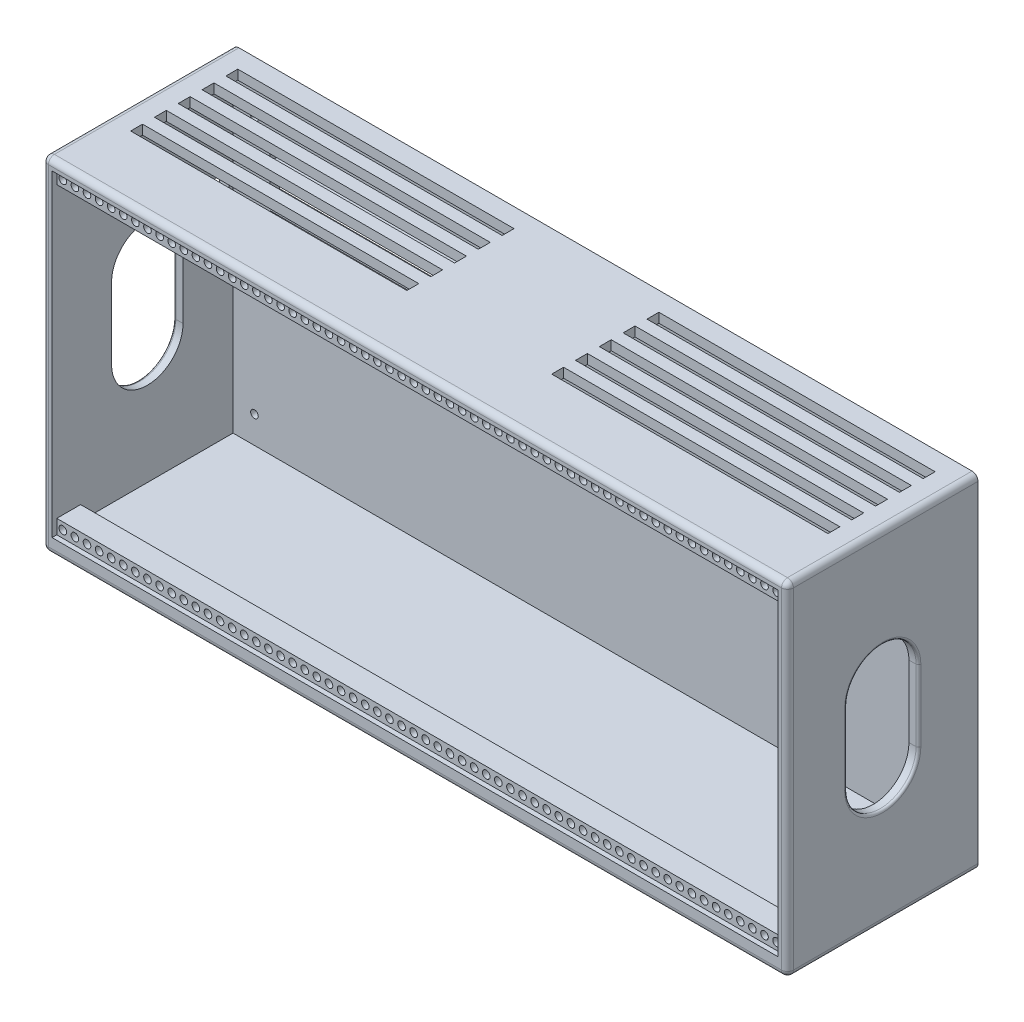
SolidWorks part; units mm, degrees
ref_plane "前视基准面" through (0, 0, 0) normal (0, 0, 1) x (1, 0, 0)
ref_plane "上视基准面" through (0, 0, 0) normal (0, 1, 0) x (1, 0, 0)
ref_plane "右视基准面" through (0, 0, 0) normal (1, 0, 0) x (0, 0, -1)
sketch "草图1" plane through (0, 0, 0) normal (0, 0, 1) x (1, 0, 0)
  line L0 (0, 0) -> (304.8, 0)
  line L2 (0, 133.35) -> (304.8, 133.35)
  line L3 (304.8, 133.35) -> (304.8, 0)
  line L4 (0, 133.35) -> (0, 137.35)
  line L5 (0, 137.35) -> (304.8, 137.35)
  line L6 (304.8, 137.35) -> (308.8, 137.35)
  line L7 (308.8, 137.35) -> (308.8, 0)
  line L8 (308.8, 0) -> (308.8, -6.6026)
  line L9 (308.8, -6.6026) -> (0, -6.6026)
  line L10 (0, -6.6026) -> (0, 0)
extrude "凸台-拉伸1" add sketch "草图1" along normal blind 80
ref_plane "基准面4" through (0, 0, 0) normal (0, 0, -1) x (-1, 0, 0)
sketch "草图2" plane through (0, 0, 0) normal (0, 0, -1) x (-1, 0, 0)
  line L0 (0, 133.35) -> (0, 0)
  line L1 (0, 0) -> (-304.8, 0)
  line L2 (-304.8, 0) -> (-304.8, 133.35)
  line L3 (-304.8, 133.35) -> (0, 133.35)
extrude "凸台-拉伸2" add sketch "草图2" against normal blind 4
ref_plane "基准面5" through (0, 0, 78) normal (0, 0, 1) x (1, 0, 0)
sketch "草图5" plane through (0, 0, 78) normal (0, 0, 1) x (1, 0, 0)
  line L0 (0, 133.35) -> (0, 127.35)
  line L1 (0, 0) -> (0, 133.35) construction
  line L2 (0, 127.35) -> (304.8, 127.35)
  line L3 (304.8, 133.35) -> (304.8, 0) construction
  line L4 (304.8, 127.35) -> (304.8, 133.35)
  line L5 (304.8, 133.35) -> (0, 133.35)
  line L6 (0, 0) -> (0, 6)
  line L7 (0, 6) -> (304.8, 6)
  line L8 (304.8, 133.35) -> (304.8, 0) construction
  line L9 (7.6, 3) -> (12.68, 3) construction
  line L10 (7.6, 130.35) -> (2.52, 130.35) construction
  line L11 (304.8, 6) -> (304.8, 0)
  line L12 (304.8, 0) -> (0, 0)
  circle A0 centre (7.6, 3) radius 1.6
  circle A1 centre (7.6, 130.35) radius 1.6
  circle A2 centre (12.68, 3) radius 1.6
  circle A3 centre (12.68, 130.35) radius 1.6
  circle A4 centre (17.76, 3) radius 1.6
  circle A5 centre (17.76, 130.35) radius 1.6
  circle A6 centre (22.84, 3) radius 1.6
  circle A7 centre (22.84, 130.35) radius 1.6
  circle A8 centre (27.92, 3) radius 1.6
  circle A9 centre (27.92, 130.35) radius 1.6
  circle A10 centre (33, 3) radius 1.6
  circle A11 centre (33, 130.35) radius 1.6
  circle A12 centre (38.08, 3) radius 1.6
  circle A13 centre (38.08, 130.35) radius 1.6
  circle A14 centre (43.16, 3) radius 1.6
  circle A15 centre (43.16, 130.35) radius 1.6
  circle A16 centre (48.24, 3) radius 1.6
  circle A17 centre (48.24, 130.35) radius 1.6
  circle A18 centre (53.32, 3) radius 1.6
  circle A19 centre (53.32, 130.35) radius 1.6
  circle A20 centre (58.4, 3) radius 1.6
  circle A21 centre (58.4, 130.35) radius 1.6
  circle A22 centre (63.48, 3) radius 1.6
  circle A23 centre (63.48, 130.35) radius 1.6
  circle A24 centre (68.56, 3) radius 1.6
  circle A25 centre (68.56, 130.35) radius 1.6
  circle A26 centre (73.64, 3) radius 1.6
  circle A27 centre (73.64, 130.35) radius 1.6
  circle A28 centre (78.72, 3) radius 1.6
  circle A29 centre (78.72, 130.35) radius 1.6
  circle A30 centre (83.8, 3) radius 1.6
  circle A31 centre (83.8, 130.35) radius 1.6
  circle A32 centre (88.88, 3) radius 1.6
  circle A33 centre (88.88, 130.35) radius 1.6
  circle A34 centre (93.96, 3) radius 1.6
  circle A35 centre (93.96, 130.35) radius 1.6
  circle A36 centre (99.04, 3) radius 1.6
  circle A37 centre (99.04, 130.35) radius 1.6
  circle A38 centre (104.12, 3) radius 1.6
  circle A39 centre (104.12, 130.35) radius 1.6
  circle A40 centre (109.2, 3) radius 1.6
  circle A41 centre (109.2, 130.35) radius 1.6
  circle A42 centre (114.28, 3) radius 1.6
  circle A43 centre (114.28, 130.35) radius 1.6
  circle A44 centre (119.36, 3) radius 1.6
  circle A45 centre (119.36, 130.35) radius 1.6
  circle A46 centre (124.44, 3) radius 1.6
  circle A47 centre (124.44, 130.35) radius 1.6
  circle A48 centre (129.52, 3) radius 1.6
  circle A49 centre (129.52, 130.35) radius 1.6
  circle A50 centre (134.6, 3) radius 1.6
  circle A51 centre (134.6, 130.35) radius 1.6
  circle A52 centre (139.68, 3) radius 1.6
  circle A53 centre (139.68, 130.35) radius 1.6
  circle A54 centre (144.76, 3) radius 1.6
  circle A55 centre (144.76, 130.35) radius 1.6
  circle A56 centre (149.84, 3) radius 1.6
  circle A57 centre (149.84, 130.35) radius 1.6
  circle A58 centre (154.92, 3) radius 1.6
  circle A59 centre (154.92, 130.35) radius 1.6
  circle A60 centre (160, 3) radius 1.6
  circle A61 centre (160, 130.35) radius 1.6
  circle A62 centre (165.08, 3) radius 1.6
  circle A63 centre (165.08, 130.35) radius 1.6
  circle A64 centre (170.16, 3) radius 1.6
  circle A65 centre (170.16, 130.35) radius 1.6
  circle A66 centre (175.24, 3) radius 1.6
  circle A67 centre (175.24, 130.35) radius 1.6
  circle A68 centre (180.32, 3) radius 1.6
  circle A69 centre (180.32, 130.35) radius 1.6
  circle A70 centre (185.4, 3) radius 1.6
  circle A71 centre (185.4, 130.35) radius 1.6
  circle A72 centre (190.48, 3) radius 1.6
  circle A73 centre (190.48, 130.35) radius 1.6
  circle A74 centre (195.56, 3) radius 1.6
  circle A75 centre (195.56, 130.35) radius 1.6
  circle A76 centre (200.64, 3) radius 1.6
  circle A77 centre (200.64, 130.35) radius 1.6
  circle A78 centre (205.72, 3) radius 1.6
  circle A79 centre (205.72, 130.35) radius 1.6
  circle A80 centre (210.8, 3) radius 1.6
  circle A81 centre (210.8, 130.35) radius 1.6
  circle A82 centre (215.88, 3) radius 1.6
  circle A83 centre (215.88, 130.35) radius 1.6
  circle A84 centre (220.96, 3) radius 1.6
  circle A85 centre (220.96, 130.35) radius 1.6
  circle A86 centre (226.04, 3) radius 1.6
  circle A87 centre (226.04, 130.35) radius 1.6
  circle A88 centre (231.12, 3) radius 1.6
  circle A89 centre (231.12, 130.35) radius 1.6
  circle A90 centre (236.2, 3) radius 1.6
  circle A91 centre (236.2, 130.35) radius 1.6
  circle A92 centre (241.28, 3) radius 1.6
  circle A93 centre (241.28, 130.35) radius 1.6
  circle A94 centre (246.36, 3) radius 1.6
  circle A95 centre (246.36, 130.35) radius 1.6
  circle A96 centre (251.44, 3) radius 1.6
  circle A97 centre (251.44, 130.35) radius 1.6
  circle A98 centre (256.52, 3) radius 1.6
  circle A99 centre (256.52, 130.35) radius 1.6
  circle A100 centre (261.6, 3) radius 1.6
  circle A101 centre (261.6, 130.35) radius 1.6
  circle A102 centre (266.68, 3) radius 1.6
  circle A103 centre (266.68, 130.35) radius 1.6
  circle A104 centre (271.76, 3) radius 1.6
  circle A105 centre (271.76, 130.35) radius 1.6
  circle A106 centre (276.84, 3) radius 1.6
  circle A107 centre (276.84, 130.35) radius 1.6
  circle A108 centre (281.92, 3) radius 1.6
  circle A109 centre (281.92, 130.35) radius 1.6
  circle A110 centre (287, 3) radius 1.6
  circle A111 centre (287, 130.35) radius 1.6
  circle A112 centre (292.08, 3) radius 1.6
  circle A113 centre (292.08, 130.35) radius 1.6
  circle A114 centre (297.16, 3) radius 1.6
  circle A115 centre (297.16, 130.35) radius 1.6
  circle A116 centre (302.24, 3) radius 1.6
  circle A117 centre (302.24, 130.35) radius 1.6
  circle A118 centre (2.52, 130.35) radius 1.6
  circle A119 centre (2.52, 3) radius 1.6
  dimension "D1" = 59
  dimension "D2" = 5.08
  dimension "D4" = 5.08
  dimension "D3" = 2
extrude "凸台-拉伸3" add sketch "草图5" against normal blind 10
ref_plane "基准面8" through (308.8, 0, 0) normal (1, 0, 0) x (0, 0, -1)
sketch "草图10" plane through (308.8, 0, 0) normal (1, 0, 0) x (0, 0, -1)
  line L3 (-40, 50.3737) -> (-40, 80.3737) construction
  line L4 (-55, 50.3737) -> (-55, 80.3737)
  line L5 (-25, 50.3737) -> (-25, 80.3737)
  arc A0 (-55, 50.3737) -> (-25, 50.3737) centre (-40, 50.3737) ccw
  arc A1 (-25, 80.3737) -> (-55, 80.3737) centre (-40, 80.3737) ccw
  point P8 (-40, 65.3737)
sketch "草图11" plane through (0, 0, 4) normal (0, 0, 1) x (1, 0, 0)
  line L0 (0, 137.35) -> (-4, 137.35)
  line L1 (-4, 137.35) -> (-4, -6.6026)
  line L2 (-4, -6.6026) -> (0, -6.6026)
  line L4 (0, -6.6026) -> (0, 137.35)
extrude "凸台-拉伸4" add sketch "草图11" along normal up to surface (76 mm away) and the other way up to surface (4 mm away) up to face at (153.4, 66.0243, 80) other way up to face at (154.4, 65.3737, 0)
sketch "草图12" plane through (0, 0, 4) normal (0, 0, 1) x (1, 0, 0)
  circle A0 centre (9, 119.35) radius 1.6
  circle A1 centre (118, 119.35) radius 1.6
  circle A2 centre (118, 55.35) radius 1.6
  circle A3 centre (9, 55.35) radius 1.6
  dimension "D1" = 2
  dimension "D2" = 2
extrude "切除-拉伸1" cut sketch "草图12" against normal through all
sketch "草图13" plane through (-4, 0, 0) normal (-1, 0, 0) x (0, 0, 1)
  circle A0 centre (10.6, 91.35) radius 5
extrude "切除-拉伸3" cut sketch "草图13" against normal up to next
sketch "草图14" plane through (0, 137.35, 0) normal (0, 1, 0) x (1, 0, 0)
  line L0 (122, -8) -> (122, -58)
  line L1 (6, -43) -> (122, -43)
  line L3 (6, -8) -> (122, -8)
  line L4 (122, -58) -> (6, -58)
  line L5 (6, -58) -> (6, -8)
  line L6 (6, -48) -> (122, -48)
  line L7 (6, -38) -> (122, -38)
  line L8 (6, -33) -> (122, -33)
  line L9 (6, -28) -> (122, -28)
  line L10 (6, -23) -> (122, -23)
  line L11 (6, -18) -> (122, -18)
  line L12 (6, -13) -> (122, -13)
  line L13 (6, -8) -> (122, -8)
  line L14 (6, -53) -> (122, -53)
  dimension "D1" = 9
  dimension "D2" = 2
extrude "切除-拉伸8" cut sketch "草图14" against normal up to next contours L5 L12 L0 L3 | L11 L5 L10 L0 | L9 L5 L8 L0 | L7 L5 L1 L0 | L5 L14 L0 L6 region at (64, 137.35, 10.5) region at (64, 137.35, 20.5) region at (64, 137.35, 30.5) region at (64, 137.35, 40.5) region at (64, 137.35, 50.5)
sketch "草图16" plane through (0, 0, 4) normal (0, 0, 1) x (1, 0, 0)
  line L0 (15.6, 106.6468) -> (111.6, 106.6468)
  line L1 (15.6, 119.35) -> (15.6, 55.35)
  line L2 (15.6, 119.35) -> (111.6, 119.35)
  line L3 (111.6, 119.35) -> (111.6, 55.35)
  line L4 (111.6, 55.35) -> (15.6, 55.35)
  line L5 (15.6, 112.6468) -> (111.6, 112.6468)
  line L6 (15.6, 100.6468) -> (111.6, 100.6468)
  line L7 (15.6, 94.6468) -> (111.6, 94.6468)
  line L8 (15.6, 88.6468) -> (111.6, 88.6468)
  line L9 (15.6, 82.6468) -> (111.6, 82.6468)
  line L10 (15.6, 76.6468) -> (111.6, 76.6468)
  line L11 (15.6, 70.6468) -> (111.6, 70.6468)
  line L12 (15.6, 64.6468) -> (111.6, 64.6468)
  line L13 (15.6, 58.6468) -> (111.6, 58.6468)
  dimension "D1" = 10
extrude "切除-拉伸10" cut sketch "草图16" against normal through all contours L1 L13 L3 L12 | L1 L11 L3 L10 | L1 L9 L3 L8 | L1 L7 L3 L6 | L5 L1 L0 L3 region at (63.6, 109.6468, 4) region at (63.6, 97.6468, 4) region at (63.6, 85.6468, 4) region at (63.6, 73.6468, 4) region at (63.6, 61.6468, 4)
extrude "切除-拉伸11" cut sketch "草图10" against normal through all contours L4 A1 L5 A0
ref_plane "基准面9" through (-4, -6.6026, 0) normal (0, 0, -1) x (-1, 0, 0)
sketch "草图23" plane through (0, -6.6026, 0) normal (0, -1, 0) x (1, 0, 0)
  text T0 "NONOHARA CASE" font "Century Gothic" height 10.5
extrude "切除-拉伸16" cut sketch "草图23" against normal blind 3
fillet "圆角4" radius 2.5 4 edges at (152.4, 137.35, 80) (-4, 65.3737, 80) (308.8, 65.3737, 80) (152.4, -6.6026, 80)
sketch "草图24" plane through (0, 0, 0) normal (0, 0, -1) x (-1, 0, 0)
  circle A0 centre (-9, 119.35) radius 1.6
  circle A1 centre (-295.8, 119.35) radius 1.6
  circle A2 centre (-9, 11.3974) radius 1.6
  circle A3 centre (-295.8, 11.3974) radius 1.6
extrude "切除-拉伸18" cut sketch "草图24" against normal through all
fillet "圆角5" radius 2.5 8 edges at (308.0678, 136.6178, 79.2678) (308.0678, -5.8704, 79.2678) (-3.2678, -5.8704, 79.2678) (-3.2678, 136.6178, 79.2678) (308.8, 137.35, 38.75) (308.8, -6.6026, 38.75) (-4, -6.6026, 38.75) (-4, 137.35, 38.75)
sketch "草图25" plane through (0, 137.35, 0) normal (0, 1, 0) x (1, 0, 0)
  line L0 (6, -43) -> (122, -43) construction
  line L1 (6, -8) -> (122, -8)
  line L2 (6, -8) -> (6, -13)
  line L3 (6, -13) -> (122, -13)
  line L4 (122, -8) -> (122, -13)
  line L5 (6, -18) -> (122, -18)
  line L6 (6, -18) -> (6, -23)
  line L7 (6, -23) -> (122, -23)
  line L8 (122, -18) -> (122, -23)
  line L9 (6, -28) -> (122, -28)
  line L10 (6, -28) -> (6, -33)
  line L11 (6, -33) -> (122, -33)
  line L12 (122, -28) -> (122, -33)
  line L13 (6, -38) -> (122, -38)
  line L14 (6, -38) -> (6, -43)
  line L15 (6, -43) -> (122, -43)
  line L16 (122, -38) -> (122, -43)
  line L18 (6, -48) -> (122, -48)
  line L19 (6, -48) -> (6, -53)
  line L20 (6, -53) -> (122, -53)
  line L21 (122, -48) -> (122, -53)
  line L25 (182.8, -48) -> (182.8, -53)
  line L26 (298.8, -53) -> (182.8, -53)
  line L27 (298.8, -48) -> (298.8, -53)
  line L28 (298.8, -48) -> (182.8, -48)
  line L29 (182.8, -38) -> (182.8, -43)
  line L30 (298.8, -43) -> (182.8, -43)
  line L31 (298.8, -38) -> (298.8, -43)
  line L32 (298.8, -38) -> (182.8, -38)
  line L33 (182.8, -28) -> (182.8, -33)
  line L34 (298.8, -33) -> (182.8, -33)
  line L35 (298.8, -28) -> (298.8, -33)
  line L36 (298.8, -28) -> (182.8, -28)
  line L37 (182.8, -18) -> (182.8, -23)
  line L38 (298.8, -23) -> (182.8, -23)
  line L39 (298.8, -18) -> (298.8, -23)
  line L40 (298.8, -18) -> (182.8, -18)
  line L41 (182.8, -8) -> (182.8, -13)
  line L42 (298.8, -13) -> (182.8, -13)
  line L43 (298.8, -8) -> (298.8, -13)
  line L44 (298.8, -8) -> (182.8, -8)
extrude "切除-拉伸19" cut sketch "草图25" against normal blind 10
fillet "圆角6" radius 1 4 edges at (-4, 35.3737, 40) (-4, 65.3737, 55) (-4, 95.3737, 40) (-4, 65.3737, 25)
fillet "圆角7" radius 1 4 edges at (308.8, 35.3737, 40) (308.8, 65.3737, 55) (308.8, 95.3737, 40) (308.8, 65.3737, 25)
